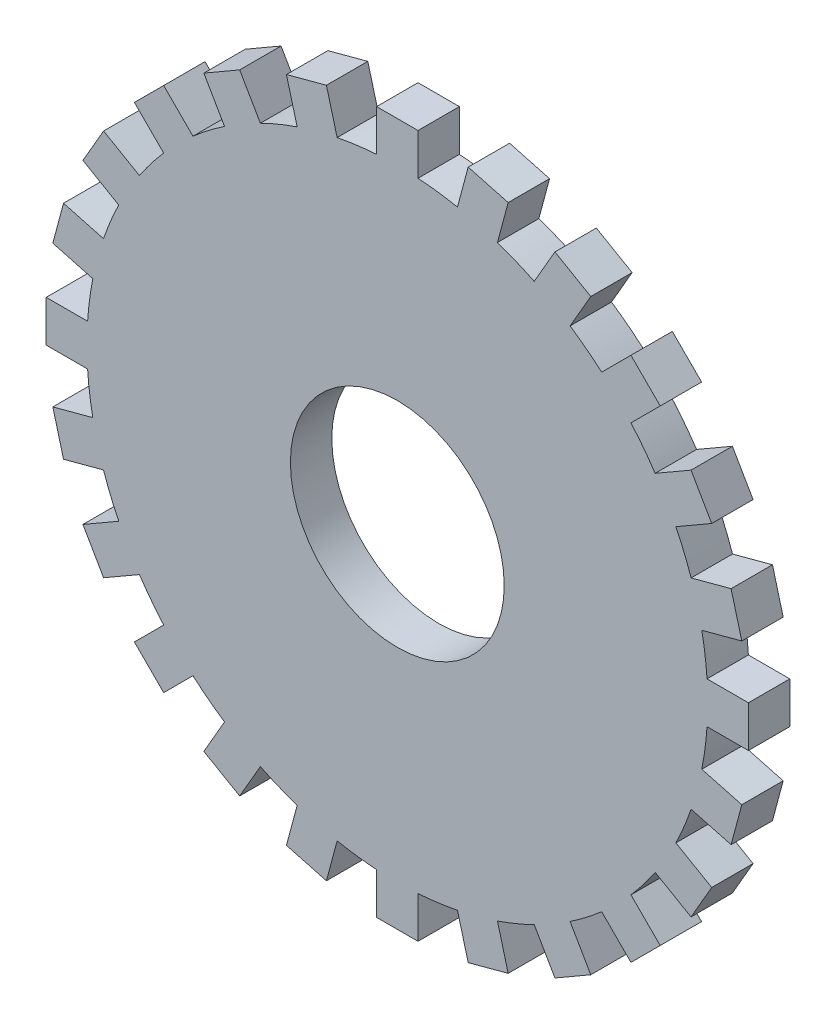
SolidWorks part; units mm, degrees
ref_plane "Front Plane" through (0, 0, 0) normal (0, 0, 1) x (1, 0, 0)
ref_plane "Top Plane" through (0, 0, 0) normal (0, 1, 0) x (1, 0, 0)
ref_plane "Right Plane" through (0, 0, 0) normal (1, 0, 0) x (0, 0, -1)
sketch "Sketch1" plane through (0, 0, 0) normal (0, 0, 1) x (1, 0, 0)
  line L0 (0, 0) -> (0, 22.5) construction
  line L1 (-1.5, 22.4499) -> (-1.5, 25.4499)
  line L2 (-1.5, 25.4499) -> (1.5, 25.4499)
  line L3 (1.5, 22.4499) -> (1.5, 25.4499)
  line L4 (-2, 7.4875) -> (-2, 19.4875)
  line L5 (-2, 19.4875) -> (2, 19.4875)
  line L6 (2, 7.4875) -> (2, 19.4875)
  circle A0 centre (0, 0) radius 22.5
  circle A1 centre (0, 0) radius 7.75
  point P8 (0, 25.4499)
  point P15 (0, 15.6071)
  point P16 (0, 19.4875)
  dimension "D2" = 45
  dimension "D4" = 15.5
  dimension "D1" = 3
  dimension "D3" = 3
  dimension "D5" = 4
  dimension "D6" = 12
extrude "Boss-Extrude1" add sketch "Sketch1" along normal mid plane 3 contours A1 L4 L5 A0 L6 | L0 A1 L6 L5 | A1 L0 L5 L4 region at (-1.0037, 13.575, 0) region at (1.0037, 13.575, 0) region at (0.7292, 21.8514, 0)
extrude "Boss-Extrude2" add sketch "Sketch1<3>" along normal mid plane 3 contours A0 L3 L2 L1 region at (0, 23.9666, 0)
sketch "Sketch1<3>" plane through (0, 0, 0) normal (0, 0, 1) x (1, 0, 0) same geometry as "Sketch1"
ref_axis "Axis1" through (0, 0, 13.2194) along (0, 0, -1)
pattern_circular "CirPattern1" count 24 over 360 about axis through (0, 0, 13.2194) along (0, 0, -1) of "Boss-Extrude2"
